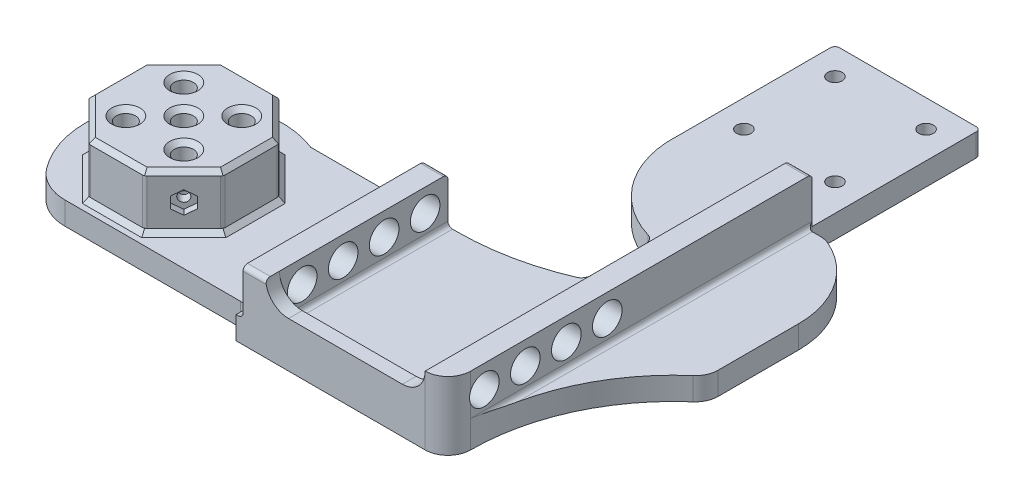
SolidWorks part; units mm, degrees
ref_plane "Спереди" through (0, 0, 0) normal (0, 0, 1) x (1, 0, 0)
ref_plane "Сверху" through (0, 0, 0) normal (0, 1, 0) x (1, 0, 0)
ref_plane "Справа" through (0, 0, 0) normal (1, 0, 0) x (0, 0, -1)
sketch "Эскиз2" plane through (0, 0, 0) normal (0, 1, 0) x (1, 0, 0)
  line L0 (0, 0) -> (32, 0)
  line L1 (0, 0) -> (0, 88)
  line L2 (32, 0) -> (32, 88)
  line L3 (0, 88) -> (32, 88)
  dimension "D1" = 88
  dimension "D2" = 32
extrude "Бобышка-Вытянуть1" add sketch "Эскиз2" along normal blind 5
sketch "Эскиз9" plane through (0, 5, 0) normal (0, 1, 0) x (1, 0, 0)
  line L0 (32, 10) -> (32, -30)
  line L1 (32, 10) -> (-68, 10)
  line L2 (32, -30) -> (-68, -30)
  line L3 (-68, 10) -> (-68, -30)
  line L4 (32, 0) -> (32, 88) construction
  line L5 (-68, -10) -> (32, -10) construction
  line L6 (32, 88) -> (0, 88) construction
  dimension "D1" = 98
  dimension "D2" = 40
  dimension "D3" = 100
extrude "Бобышка-Вытянуть6" add sketch "Эскиз9" against normal blind 5
sketch "Эскиз11" plane through (0, 5, 0) normal (0, 1, 0) x (1, 0, 0)
  line L0 (-46, -10) -> (-46, -19) construction
  line L1 (-46, -10) -> (-46, -1) construction
  line L2 (-46, -10) -> (-52.364, -3.636) construction
  line L3 (-46, -10) -> (-52.364, -16.364) construction
  line L6 (-68, -10) -> (32, -10) construction
  line L7 (-68, 10) -> (-68, -30) construction
  line L8 (32, -30) -> (32, 88) construction
  circle A0 centre (-46, -10) radius 9 construction
  circle A1 centre (-52.364, -3.636) radius 2.1
  circle A2 centre (-39.636, -3.636) radius 2.1
  circle A3 centre (-39.636, -16.364) radius 2.1
  circle A4 centre (-52.364, -16.364) radius 2.1
  circle A5 centre (-46, -10) radius 2.1
  point P22 (-46, -10)
  dimension "D1" = 22
  dimension "D3" = 18
  dimension "D4" = 4.2
  dimension "D5" = 4
  dimension "D2" = 45
  dimension "D7" = 4.2
extrude "Вырез-Вытянуть3" cut sketch "Эскиз11" against normal up to surface (5 mm away) up to face at (-12, 0, -22.6667)
sketch "Эскиз12" plane through (0, 0, 0) normal (0, -1, 0) x (1, 0, 0)
  circle A0 centre (-52.364, 3.636) radius 2.1 construction
  circle A1 centre (-52.364, 3.636) radius 2.1 construction
  circle A2 centre (-39.636, 3.636) radius 2.1 construction
  circle A3 centre (-39.636, 3.636) radius 2.1 construction
  circle A8 centre (-46, 10) radius 19.5
  circle A9 centre (-46, 10) radius 21.5
  circle A10 centre (-39.636, 16.364) radius 2.1 construction
  circle A11 centre (-39.636, 16.364) radius 2.1 construction
  circle A12 centre (-52.364, 16.364) radius 2.1 construction
  circle A13 centre (-52.364, 16.364) radius 2.1 construction
  circle A14 centre (-46, 10) radius 9 construction
  dimension "D1" = 39
  dimension "D2" = 43
extrude "Бобышка-Вытянуть7" add sketch "Эскиз12" along normal blind 8
sketch "Эскиз13" plane through (0, 5, 0) normal (0, 1, 0) x (1, 0, 0)
  line L0 (6, 81) -> (26, 81) construction
  line L1 (6, 81) -> (6, 61) construction
  line L2 (26, 81) -> (26, 61) construction
  line L3 (6, 61) -> (26, 61) construction
  line L4 (16, 81) -> (16, 61) construction
  line L5 (16, 88) -> (16, -30) construction
  line L6 (32, 88) -> (0, 88) construction
  line L7 (-68, -30) -> (32, -30) construction
  circle A0 centre (6, 81) radius 1.6
  circle A1 centre (6, 61) radius 1.6
  circle A2 centre (26, 61) radius 1.6
  circle A3 centre (26, 81) radius 1.6
  dimension "D4" = 3.2
  dimension "D5" = 3.2
  dimension "D6" = 3.2
  dimension "D7" = 3.2
  dimension "D1" = 20
  dimension "D2" = 20
  dimension "D3" = 7
extrude "Вырез-Вытянуть4" cut sketch "Эскиз13" against normal through all
sketch "Sketch1" plane through (0, 0, -88) normal (0, 0, -1) x (-1, 0, 0)
  line L4 (-32, 0) -> (0, 0)
  line L5 (0, 0) -> (0, 5)
  line L6 (0, 5) -> (-32, 5)
  line L7 (-32, 5) -> (-32, 0)
  line L8 (-32, 0) -> (0, 0)
  line L9 (0, 0) -> (0, 5)
  line L10 (0, 5) -> (-32, 5)
  line L11 (-32, 5) -> (-32, 0)
  dimension "D1" = 0
extrude "Cut-Extrude1" cut sketch "Sketch1" against normal blind 1
sketch "Эскиз14" plane through (0, 0, 0) normal (0, -1, 0) x (1, 0, 0)
  line L3 (-53.8899, 30) -> (-68, 30)
  line L4 (-68, 30) -> (-68, -10)
  line L5 (-68, -10) -> (-53.8899, -10)
  line L6 (-53.8899, 30) -> (-68, 30)
  line L7 (-68, 30) -> (-68, -10)
  line L8 (-68, -10) -> (-53.8899, -10)
  arc A1 (-53.8899, 30) -> (-53.8899, -10) centre (-46, 10) ccw
  arc A2 (-53.8899, 30) -> (-53.8899, -10) centre (-46, 10) ccw
  dimension "D1" = 0
extrude "Вырез-Вытянуть5" cut sketch "Эскиз14" against normal through all
sketch "Эскиз15" plane through (0, 0, 0) normal (0, 1, 0) x (1, 0, 0)
  line L1 (-38.1101, -30) -> (-53.8899, -30)
  line L2 (-38.1101, -30) -> (-53.8899, -30)
  line L3 (-53.8899, 10) -> (-38.1101, 10)
  line L4 (-53.8899, 10) -> (-38.1101, 10)
  arc A1 (-53.8899, -30) -> (-38.1101, -30) centre (-46, -10) ccw
  arc A2 (-53.8899, -30) -> (-38.1101, -30) centre (-46, -10) ccw
  arc A3 (-38.1101, 10) -> (-53.8899, 10) centre (-46, -10) ccw
  arc A4 (-38.1101, 10) -> (-53.8899, 10) centre (-46, -10) ccw
  dimension "D1" = 0
  dimension "D2" = 0
extrude "Бобышка-Вытянуть8" add sketch "Эскиз15" along normal up to surface (5 mm away) up to face at (-52.364, 5, 5.736)
sketch "Эскиз16" plane through (0, 5, 0) normal (0, 1, 0) x (1, 0, 0)
  line L0 (-13, 10) -> (-8, 10)
  line L1 (-13, 10) -> (-13, -30)
  line L2 (-8, 10) -> (-8, -30)
  line L3 (-13, -30) -> (-8, -30)
  line L4 (0, 10) -> (-38.1101, 10) construction
  line L5 (-38.1101, -30) -> (32, -30) construction
  line L6 (32, -30) -> (32, 87) construction
  line L7 (27, -30) -> (32, -30)
  line L8 (27, -30) -> (27, 50)
  line L9 (32, -30) -> (32, 50)
  line L10 (27, 50) -> (32, 50)
  dimension "D1" = 5
  dimension "D2" = 45
  dimension "D3" = 5
  dimension "D4" = 80
extrude "Бобышка-Вытянуть9" add sketch "Эскиз16" along normal blind 10
sketch "Эскиз17" plane through (0, 5, 0) normal (0, 1, 0) x (1, 0, 0)
  line L0 (-8, -30) -> (-8, -27)
  line L1 (-8, -30) -> (27, -30)
  line L2 (-8, -27) -> (27, -27)
  line L3 (27, -30) -> (27, -27)
  line L4 (-8, -30) -> (-8, 10) construction
  line L5 (27, 50) -> (27, -30) construction
  dimension "D1" = 3
extrude "Бобышка-Вытянуть10" add sketch "Эскиз17" along normal blind 5
sketch "Эскиз18" plane through (-8, 0, 0) normal (1, 0, 0) x (0, 0, -1)
  line L0 (10, 10) -> (-41.8716, 10) construction
  line L1 (10, 15) -> (10, 5) construction
  circle A0 centre (5, 10) radius 3.25
  circle A1 centre (-4, 10) radius 3.25
  circle A2 centre (-13, 10) radius 3.25
  circle A3 centre (-22, 10) radius 3.25
  dimension "D1" = 6.5
  dimension "D2" = 6.5
  dimension "D3" = 6.5
  dimension "D4" = 6.5
  dimension "D5" = 5
  dimension "D6" = 9
  dimension "D7" = 9
  dimension "D8" = 9
extrude "Вырез-Вытянуть6" cut sketch "Эскиз18" against normal through all
sketch "Эскиз19" plane through (32, 0, 0) normal (1, 0, 0) x (0, 0, -1)
  line L0 (50, 10) -> (-21.4049, 10) construction
  line L1 (50, 15) -> (50, 5) construction
  circle A0 centre (41, 10) radius 3.25
  circle A1 centre (32, 10) radius 3.25
  circle A2 centre (23, 10) radius 3.25
  circle A3 centre (14, 10) radius 3.25
  dimension "D1" = 6.5
  dimension "D2" = 6.5
  dimension "D3" = 6.5
  dimension "D4" = 6.5
  dimension "D5" = 9
  dimension "D6" = 9
  dimension "D7" = 9
  dimension "D8" = 9
fillet "Скругление5" radius 1 4 edges at (27, 5, -11.5) (9.5, 5, 27)
fillet "Скругление6" radius 5 2 edges at (27, 10, 28.5) (-8, 10, 28.5)
fillet "Скругление7" radius 1 2 edges at (32, 2.5, -87) (0, 2.5, -87)
fillet "Скругление8" radius 1 3 edges at (-10.5, 15, 30) (-10.5, 15, -10) (29.5, 15, -50)
sketch "Эскиз20" plane through (0, -8, 0) normal (0, -1, 0) x (1, 0, 0)
  circle A1 centre (-46, 10) radius 21.5
  circle A2 centre (-46, 10) radius 21.5
  dimension "D1" = 0
extrude "Вырез-Вытянуть8" cut sketch "Эскиз20" against normal up to surface (8 mm away) up to face at (26, 0, -82.6)
sketch "Эскиз21" plane through (0, 5, 0) normal (0, 1, 0) x (1, 0, 0)
  line L0 (-59.1624, -27) -> (-16.5, -27)
  line L1 (-38.1101, -30) -> (-14, -30) construction
  line L2 (-13, 10) -> (-13, -30) construction
  line L3 (-38.1101, -30) -> (-14.5, -30)
  line L4 (-14.5, -30) -> (-14.5, -29)
  arc A0 (-38.1101, 10) -> (-38.1101, -30) centre (-46, -10) ccw construction
  arc A1 (-14.5, -29) -> (-16.5, -27) centre (-16.5, -29) ccw
  arc A2 (-59.1624, -27) -> (-38.1101, -30) centre (-46, -10) ccw
  dimension "D1" = 3
  dimension "D2" = 2
  dimension "D3" = 1.5
extrude "Вырез-Вытянуть9" cut sketch "Эскиз21" against normal through all
fillet "Скругление9" radius 10 1 edges at (-59.1624, 2.5, 27)
sketch "Эскиз22" plane through (0, 0, 0) normal (-1, 0, 0) x (0, 0, 1)
  line L0 (-50, 14) -> (-50, 6) construction
  line L1 (-50, 5) -> (-50, 0) construction
  line L2 (-86, 5) -> (-10, 5) construction
  line L3 (-86, 0) -> (-10, 0) construction
  line L4 (-50, 5) -> (-10, 5)
  line L5 (-50, 0) -> (-10, 0)
  line L6 (-10, 0) -> (-10, 5) construction
  line L7 (-10, 0) -> (-10, 5)
  line L8 (-50, 5) -> (-50, 0)
extrude "Вырез-Вытянуть10" cut sketch "Эскиз22" against normal blind 17
sketch "Эскиз23" plane through (32, 0, 0) normal (1, 0, 0) x (0, 0, -1)
  line L4 (10, 5) -> (10, 0)
  line L5 (50, 5) -> (10, 5)
  line L6 (50, 0) -> (50, 5)
  line L7 (10, 0) -> (50, 0)
  line L8 (10, 5) -> (10, 0)
  line L9 (50, 5) -> (10, 5)
  line L10 (50, 0) -> (50, 5)
  line L11 (10, 0) -> (50, 0)
  dimension "D1" = 0
extrude "Бобышка-Вытянуть11" add sketch "Эскиз23" along normal blind 17
sketch "Эскиз25" plane through (0, 5, 0) normal (0, 1, 0) x (1, 0, 0)
  line L0 (17, 15) -> (17, 10)
  line L1 (17, 10) -> (17, 50) construction
  line L2 (17, 10) -> (-6, 10)
  line L3 (17, 10) -> (-7, 10) construction
  line L6 (17, 30) -> (17, 50)
  line L7 (17, 50) -> (0, 50)
  arc A0 (17, 30) -> (0, 50) centre (21.9531, 51.4352) cw
  arc A1 (17, 15) -> (-6, 10) centre (-6, 65.4) cw
  dimension "D4" = 22
  dimension "D1" = 5
  dimension "D2" = 23
  dimension "D3" = 15
  dimension "D5" = 20
extrude "Бобышка-Вытянуть12" add sketch "Эскиз25" against normal up to surface (5 mm away) up to face at (4.3102, 0, -23.8502)
fillet "Скругление10" radius 2 2 edges at (17, 2.5, -15) (17, 2.5, -30)
sketch "Эскиз26" plane through (0, 5, 0) normal (0, 1, 0) x (1, 0, 0)
  line L0 (32, 30) -> (49, 30) construction
  line L1 (32, 50) -> (32, 10) construction
  line L3 (49, 50) -> (49, 10) construction
  line L4 (32, 50) -> (32, 30) construction
  line L5 (49, 50) -> (32, 50) construction
  line L6 (49, 50) -> (32, 50)
  line L7 (49, 50) -> (49, 30)
  arc A0 (49, 30) -> (32, 50) centre (28.7353, 30) ccw
  dimension "D1" = 20
extrude "Вырез-Вытянуть11" cut sketch "Эскиз26" against normal through all
sketch "Эскиз27" plane through (0, 5, 0) normal (0, 1, 0) x (1, 0, 0)
  line L0 (49, 10) -> (32, 10) construction
  line L1 (49, 10) -> (32, 10)
  line L2 (32, 10) -> (32, -25)
  arc A0 (49, 10) -> (32, -25) centre (76.5294, -25) ccw
  dimension "D1" = 35
extrude "Бобышка-Вытянуть13" add sketch "Эскиз27" against normal up to surface (5 mm away) up to face at (4.9703, 0, -21.3596)
fillet "Скругление12" radius 5 1 edges at (32, 7.5, 30)
fillet "Скругление13" radius 1 1 edges at (32, 5, -12.5)
sketch "Эскиз28" plane through (32, 0, 0) normal (1, 0, 0) x (0, 0, -1)
  circle A0 centre (5, 10) radius 3.25 construction
  circle A1 centre (-4, 10) radius 3.25 construction
  circle A2 centre (-13, 10) radius 3.25 construction
  circle A3 centre (-22, 10) radius 3.25 construction
  circle A4 centre (5, 10) radius 3.25
  circle A5 centre (-4, 10) radius 3.25
  circle A6 centre (-13, 10) radius 3.25
  circle A7 centre (-22, 10) radius 3.25
extrude "Вырез-Вытянуть12" cut sketch "Эскиз28" against normal up to surface (5 mm away) up to face at (27, 11.2414, -19.0414)
fillet "Скругление14" radius 5 1 edges at (49, 2.5, -10)
sketch "Эскиз29" plane through (0, 0, -50) normal (0, 0, -1) x (-1, 0, 0)
  line L0 (-32, 0) -> (-32, 5) construction
  line L1 (-32, 0) -> (-32, 8)
  line L2 (-32, 14) -> (-32, 6) construction
  line L3 (-32, 8) -> (-37, 8)
  line L4 (-37, 8) -> (-37, 0)
  line L5 (-37, 0) -> (-32, 0)
  dimension "D1" = 5
  dimension "D2" = 8
extrude "Вырез-Вытянуть13" cut sketch "Эскиз29" against normal blind 1
fillet "Скругление15" radius 1 1 edges at (32, 3, -49)
fillet "Скругление16" radius 5 1 edges at (35.7822, 2.5, -49)
sketch "Эскиз33" plane through (0, 5, 0) normal (0, 1, 0) x (1, 0, 0)
  line L0 (-46, -10) -> (-46, 4.75) construction
  line L1 (-52.1097, -24.75) -> (-39.8903, -24.75)
  line L2 (-39.8903, -24.75) -> (-31.25, -16.1097)
  line L3 (-31.25, -16.1097) -> (-31.25, -3.8903)
  line L4 (-31.25, -3.8903) -> (-39.8903, 4.75)
  line L5 (-39.8903, 4.75) -> (-52.1097, 4.75)
  line L6 (-52.1097, 4.75) -> (-60.75, -3.8903)
  line L7 (-60.75, -3.8903) -> (-60.75, -16.1097)
  line L8 (-60.75, -16.1097) -> (-52.1097, -24.75)
  line L9 (-16.5, -27) -> (-55.1241, -27) construction
  circle A0 centre (-46, -10) radius 14.75 construction
  circle A2 centre (-52.364, -3.636) radius 2.1 construction
  circle A3 centre (-46, -10) radius 2.1 construction
  circle A4 centre (-52.364, -16.364) radius 2.1 construction
  circle A5 centre (-39.636, -3.636) radius 2.1 construction
  circle A6 centre (-39.636, -16.364) radius 2.1 construction
  circle A7 centre (-52.364, -3.636) radius 2.1
  circle A8 centre (-46, -10) radius 2.1
  circle A9 centre (-52.364, -16.364) radius 2.1
  circle A10 centre (-39.636, -3.636) radius 2.1
  circle A11 centre (-39.636, -16.364) radius 2.1
  dimension "D1" = 2.25
extrude "Бобышка-Вытянуть15" add sketch "Эскиз33" along normal blind 12
sketch "Эскиз37" plane through (-7.5702, 0, -7.5702) normal (0.7071, 0, 0.7071) x (0.7071, 0, -0.7071)
  line L0 (-39.598, 17) -> (-39.598, 5) construction
  line L1 (-45.7076, 17) -> (-33.4883, 17) construction
  line L2 (-45.7076, 5) -> (-33.4883, 5) construction
  circle A0 centre (-39.598, 11) radius 1.1
  dimension "D1" = 2.2
extrude "Вырез-Вытянуть15" cut sketch "Эскиз37" against normal up to surface (3.9611 mm away) up to face at (-39.636, 0, 14.264)
sketch "Эскиз38" plane through (-7.5702, 0, -7.5702) normal (0.7071, 0, 0.7071) x (0.7071, 0, -0.7071)
  line L0 (-39.598, 11) -> (-39.598, 13.4249) construction
  line L1 (-39.598, 8.5751) -> (-37.498, 9.7876)
  line L2 (-37.498, 9.7876) -> (-37.498, 12.2124)
  line L3 (-37.498, 12.2124) -> (-39.598, 13.4249)
  line L4 (-39.598, 13.4249) -> (-41.698, 12.2124)
  line L5 (-41.698, 12.2124) -> (-41.698, 9.7876)
  line L6 (-41.698, 9.7876) -> (-39.598, 8.5751)
  circle A0 centre (-39.598, 11) radius 2.1 construction
  dimension "D1" = 4.2
extrude "Вырез-Вытянуть16" cut sketch "Эскиз38" against normal blind 1.6
sketch "Эскиз39" plane through (-38.4298, 0, 38.4298) normal (-0.7071, 0, 0.7071) x (0.7071, 0, 0.7071)
  line L0 (-25.4558, 17) -> (-25.4558, 5) construction
  line L1 (-31.5655, 17) -> (-19.3462, 17) construction
  line L2 (-31.5655, 5) -> (-19.3462, 5) construction
  circle A0 centre (-25.4558, 11) radius 1.1
  dimension "D1" = 2.2
extrude "Вырез-Вытянуть17" cut sketch "Эскиз39" against normal up to surface (3.9611 mm away) up to face at (-52.364, 0, 14.264)
sketch "Эскиз41" plane through (-38.4298, 0, 38.4298) normal (-0.7071, 0, 0.7071) x (0.7071, 0, 0.7071)
  line L0 (-25.4558, 11) -> (-25.4558, 13.4249) construction
  line L1 (-25.4558, 8.5751) -> (-23.3558, 9.7876)
  line L2 (-23.3558, 9.7876) -> (-23.3558, 12.2124)
  line L3 (-23.3558, 12.2124) -> (-25.4558, 13.4249)
  line L4 (-25.4558, 13.4249) -> (-27.5558, 12.2124)
  line L5 (-27.5558, 12.2124) -> (-27.5558, 9.7876)
  line L6 (-27.5558, 9.7876) -> (-25.4558, 8.5751)
  circle A0 centre (-25.4558, 11) radius 2.1 construction
  dimension "D1" = 4.2
extrude "Вырез-Вытянуть18" cut sketch "Эскиз41" against normal blind 1.6
sketch "Эскиз42" plane through (-60.75, 0, 0) normal (-1, 0, 0) x (0, 0, 1)
  line L0 (10, 17) -> (10, 5) construction
  line L1 (3.8903, 17) -> (16.1097, 17) construction
  line L2 (3.8903, 5) -> (16.1097, 5) construction
  circle A0 centre (10, 11) radius 1.1
  dimension "D1" = 2.2
extrude "Вырез-Вытянуть19" cut sketch "Эскиз42" against normal up to surface (12.9611 mm away) up to face at (-46, 0, 7.9)
sketch "Эскиз43" plane through (-60.75, 0, 0) normal (-1, 0, 0) x (0, 0, 1)
  line L0 (10, 11) -> (10, 13.4249) construction
  line L1 (10, 13.4249) -> (7.9, 12.2124)
  line L2 (7.9, 12.2124) -> (7.9, 9.7876)
  line L3 (7.9, 9.7876) -> (10, 8.5751)
  line L4 (10, 8.5751) -> (12.1, 9.7876)
  line L5 (12.1, 9.7876) -> (12.1, 12.2124)
  line L6 (12.1, 12.2124) -> (10, 13.4249)
  circle A0 centre (10, 11) radius 2.1 construction
  dimension "D1" = 4.2
extrude "Вырез-Вытянуть20" cut sketch "Эскиз43" against normal blind 1.6
sketch "Эскиз44" plane through (-28.4298, 0, -28.4298) normal (-0.7071, 0, -0.7071) x (-0.7071, 0, 0.7071)
  line L0 (39.598, 17) -> (39.598, 5) construction
  line L1 (33.4883, 17) -> (45.7076, 17) construction
  line L2 (33.4883, 5) -> (45.7076, 5) construction
  circle A0 centre (39.598, 11) radius 1.1
  dimension "D1" = 2.2
extrude "Вырез-Вытянуть21" cut sketch "Эскиз44" against normal up to surface (3.9611 mm away) up to face at (-52.364, 0, 1.536)
sketch "Эскиз45" plane through (-28.4298, 0, -28.4298) normal (-0.7071, 0, -0.7071) x (-0.7071, 0, 0.7071)
  line L0 (39.598, 11) -> (39.598, 13.4249) construction
  line L1 (39.598, 13.4249) -> (37.498, 12.2124)
  line L2 (37.498, 12.2124) -> (37.498, 9.7876)
  line L3 (37.498, 9.7876) -> (39.598, 8.5751)
  line L4 (39.598, 8.5751) -> (41.698, 9.7876)
  line L5 (41.698, 9.7876) -> (41.698, 12.2124)
  line L6 (41.698, 12.2124) -> (39.598, 13.4249)
  circle A0 centre (39.598, 11) radius 2.1 construction
  dimension "D1" = 4.2
extrude "Вырез-Вытянуть22" cut sketch "Эскиз45" against normal blind 1.6
sketch "Эскиз46" plane through (-17.5702, 0, 17.5702) normal (0.7071, 0, -0.7071) x (-0.7071, 0, -0.7071)
  line L0 (25.4558, 17) -> (25.4558, 5) construction
  line L1 (19.3462, 17) -> (31.5655, 17) construction
  line L2 (19.3462, 5) -> (31.5655, 5) construction
  circle A0 centre (25.4558, 11) radius 1.1
  dimension "D1" = 2.2
extrude "Вырез-Вытянуть23" cut sketch "Эскиз46" against normal up to surface (3.9611 mm away) up to face at (-39.636, 0, 1.536)
sketch "Эскиз47" plane through (-17.5702, 0, 17.5702) normal (0.7071, 0, -0.7071) x (-0.7071, 0, -0.7071)
  line L0 (25.4558, 11) -> (25.4558, 13.4249) construction
  line L1 (25.4558, 13.4249) -> (23.3558, 12.2124)
  line L2 (23.3558, 12.2124) -> (23.3558, 9.7876)
  line L3 (23.3558, 9.7876) -> (25.4558, 8.5751)
  line L4 (25.4558, 8.5751) -> (27.5558, 9.7876)
  line L5 (27.5558, 9.7876) -> (27.5558, 12.2124)
  line L6 (27.5558, 12.2124) -> (25.4558, 13.4249)
  circle A0 centre (25.4558, 11) radius 2.1 construction
  dimension "D1" = 4.2
extrude "Вырез-Вытянуть24" cut sketch "Эскиз47" against normal blind 1.6
chamfer "Фаска1" distance 1 angle 45 8 edges at (-35.5702, 5, 20.4298) (-31.25, 5, 10) (-35.5702, 5, -0.4298) (-46, 5, -4.75) (-56.4298, 5, -0.4298) (-60.75, 5, 10) (-56.4298, 5, 20.4298) (-46, 5, 24.75)
chamfer "Фаска2" distance 1 angle 45 13 edges at (-39.636, 17, 18.464) (-52.364, 17, 18.464) (-52.364, 17, 5.736) (-60.75, 17, 10) (-56.4298, 17, -0.4298) (-46, 17, -4.75) (-35.5702, 17, -0.4298) (-31.25, 17, 10) (-35.5702, 17, 20.4298) (-46, 17, 24.75) (-56.4298, 17, 20.4298) (-46, 17, 12.1) (-39.636, 17, 5.736)
fillet "Скругление17" radius 1 8 edges at (-39.8903, 11, -4.75) (-31.25, 11, 3.8903) (-31.25, 11, 16.1097) (-39.8903, 11, 24.75) (-52.1097, 11, 24.75) (-60.75, 11, 16.1097) (-52.1097, 11, -4.75) (-60.75, 11, 3.8903)
